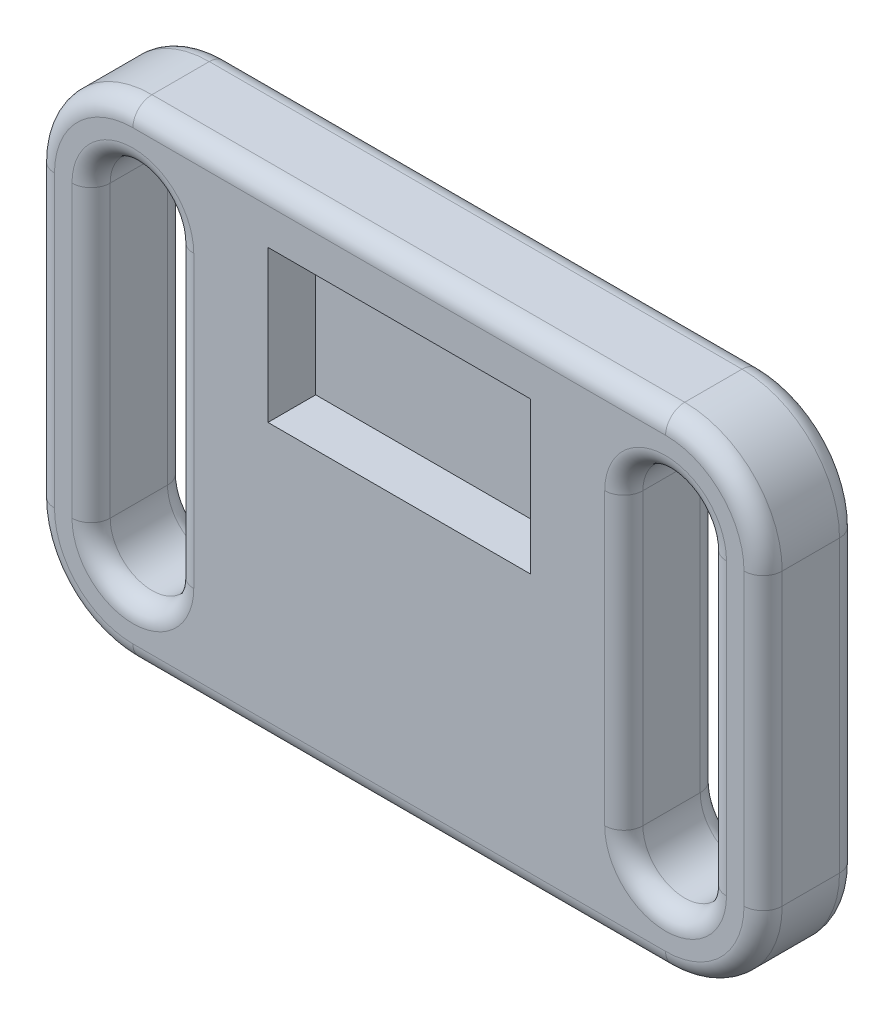
SolidWorks part; units mm, degrees
ref_plane "Front Plane" through (0, 0, 0) normal (0, 0, 1) x (1, 0, 0)
ref_plane "Top Plane" through (0, 0, 0) normal (0, 1, 0) x (1, 0, 0)
ref_plane "Right Plane" through (0, 0, 0) normal (1, 0, 0) x (0, 0, -1)
sketch "Sketch1" plane through (0, 0, 0) normal (0, 0, 1) x (1, 0, 0)
  line L0 (-152.4, -60.7667) -> (-152.4, 60.7667)
  line L1 (-152.4, -101.6) -> (152.4, -101.6) construction
  line L2 (-152.4, -101.6) -> (-152.4, 101.6) construction
  line L3 (-152.4, 101.6) -> (152.4, 101.6) construction
  line L4 (152.4, -101.6) -> (152.4, 101.6) construction
  line L5 (-152.4, -101.6) -> (152.4, 101.6) construction
  line L6 (-152.4, 101.6) -> (152.4, -101.6) construction
  line L7 (-111.5667, 101.6) -> (111.5667, 101.6)
  line L8 (0, 101.6) -> (0, -101.6) construction
  line L9 (152.4, 0) -> (-152.4, 0) construction
  line L10 (-152.4, -101.6) -> (152.4, 101.6) construction
  line L11 (-152.4, -101.6) -> (152.4, -101.6) construction
  line L12 (-111.5667, -101.6) -> (111.5667, -101.6)
  line L13 (152.4, -101.6) -> (-152.4, 101.6) construction
  line L14 (152.4, 101.6) -> (-152.4, -101.6) construction
  line L15 (152.4, -101.6) -> (-152.4, 101.6) construction
  line L16 (152.4, -101.6) -> (152.4, 101.6) construction
  line L17 (152.4, -60.7667) -> (152.4, 60.7667)
  line L18 (-129.0667, 60.7667) -> (-152.4, 60.7667) construction
  line L19 (-129.0667, 60.7667) -> (-94.0667, 60.7667) construction
  line L20 (-129.0667, 60.7667) -> (-129.0667, -60.7667)
  line L21 (-129.0667, -60.7667) -> (-94.0667, -60.7667) construction
  line L22 (-94.0667, 60.7667) -> (-94.0667, -60.7667)
  line L23 (129.0667, 60.7667) -> (129.0667, -60.7667)
  line L24 (94.0667, 60.7667) -> (94.0667, -60.7667)
  arc A0 (-152.4, 60.7667) -> (-111.5667, 101.6) centre (-111.5667, 60.7667) cw
  arc A1 (-152.4, -60.7667) -> (-111.5667, -101.6) centre (-111.5667, -60.7667) ccw
  arc A2 (152.4, -60.7667) -> (111.5667, -101.6) centre (111.5667, -60.7667) cw
  arc A3 (152.4, 60.7667) -> (111.5667, 101.6) centre (111.5667, 60.7667) ccw
  arc A4 (-129.0667, 60.7667) -> (-94.0667, 60.7667) centre (-111.5667, 60.7667) cw
  arc A5 (-129.0667, -60.7667) -> (-94.0667, -60.7667) centre (-111.5667, -60.7667) ccw
  arc A6 (129.0667, -60.7667) -> (94.0667, -60.7667) centre (111.5667, -60.7667) cw
  arc A7 (129.0667, 60.7667) -> (94.0667, 60.7667) centre (111.5667, 60.7667) ccw
  point P0 (0, 0)
  point P17 (0, 0)
  dimension "D1" = 203.2
  dimension "D2" = 304.8
  dimension "D3" = 35
  dimension "D4" = 23.3333
extrude "Steering Wheel Body" add sketch "Sketch1" along normal mid plane 40
fillet "Fillet1" radius 8 32 edges at (111.5667, 78.2667, -20) (129.0667, 0, -20) (111.5667, -78.2667, -20) (94.0667, 0, -20) (-111.5667, -78.2667, -20) (-129.0667, 0, -20) (-111.5667, 78.2667, -20) (-94.0667, 0, -20) (-152.4, 0, -20) (-140.4402, -89.6402, -20) (0, -101.6, -20) (140.4402, -89.6402, -20) (152.4, 0, -20) (140.4402, 89.6402, -20) (0, 101.6, -20) (-140.4402, 89.6402, -20) (129.0667, 0, 20) (111.5667, 78.2667, 20) (94.0667, 0, 20) (111.5667, -78.2667, 20) (0, 101.6, 20) (140.4402, 89.6402, 20) (152.4, 0, 20) (140.4402, -89.6402, 20) (0, -101.6, 20) (-140.4402, -89.6402, 20) (-152.4, 0, 20) (-140.4402, 89.6402, 20) (-129.0667, 0, 20) (-111.5667, -78.2667, 20) (-94.0667, 0, 20) (-111.5667, 78.2667, 20)
sketch "Sketch3" plane through (0, 0, 0) normal (0, 0, 1) x (1, 0, 0)
  line L0 (0, 0) -> (0, 101.6) construction
  line L1 (-54.9926, 15) -> (54.9926, 15)
  line L2 (-54.9926, 15) -> (-54.9926, 78.5)
  line L3 (-54.9926, 78.5) -> (54.9926, 78.5)
  line L4 (54.9926, 15) -> (54.9926, 78.5)
  line L5 (111.5667, 101.6) -> (-111.5667, 101.6) construction
  line L6 (0, 0) -> (152.4, 0) construction
  line L7 (152.4, -60.7667) -> (152.4, 60.7667) construction
  line L8 (-94.0667, -60.7667) -> (-94.0667, 60.7667) construction
  line L9 (-54.9926, 15) -> (54.9926, 78.5) construction
  point P9 (0, 15)
  dimension "D3" = 15
  dimension "D1" = 127
  dimension "D2" = 30
extrude "LCD Cutout" cut sketch "Sketch3" against normal blind 20 from surface starting at face at (111.5667, 0, 20)
sketch "Sketch5" plane through (0, 0, 0) normal (0, 0, 1) x (1, 0, 0)
  line L0 (0, 0) -> (0, 41.9601) construction
  circle A0 centre (0, 0) radius 41.9601 construction
  point P5 (0, 41.9601)
  dimension "D1" = 83.9201
hole_wizard "M5x0.8 Tapped Hole1" positions "Sketch6" profile "Sketch7" tap size "M5x0.8" standard "ANSI Metric"
sketch "Sketch6" plane through (0, 0, -20) normal (0, 0, -1) x (-1, 0, 0)
  point P0 (0, 41.9601)
sketch "Sketch7" plane through (0, 41.9601, -20) normal (1, 0, 0) x (0, 1, 0)
  line L0 (0, 0) -> (0, 9.6618)
  line L1 (0, 9.6618) -> (2.1, 8.4)
  line L2 (2.1, 8.4) -> (2.1, 0)
  line L5 (2.1, 0) -> (0, 0)
  line L10 (0, 9.6618) -> (-2.1, 8.4) construction
  line L11 (0, -6.35) -> (0, 107.95) construction
  dimension "Tap Drill Dia." = 4.2
  dimension "Tap Drill Depth" = 8.4
  dimension "Drill Angle" = 118
sketch "Sketch8" plane through (0, 0, 0) normal (0, 1, 0) x (1, 0, 0)
  line L0 (0, 52.4568) -> (0, -56.5569) construction
pattern_circular "CirPattern1" count 9 over 360 about axis through (0, 0, -52.4568) along (0, 0, 1) of "M5x0.8 Tapped Hole1"
equation "\"Steering Wheel Height\"= 8in"
equation "\"D1@Sketch1\"=\"Steering Wheel Height\""
equation "\"Steering Wheel Width\"= 12in"
equation "\"D2@Sketch1\"=\"Steering Wheel Width\""
equation "\"Steering Wheel Thickness\"= 35mm"
equation "\"Hand Cutout Width\"= 35mm"
equation "\"D3@Sketch1\"=\"Hand Cutout Width\""
equation "\"D4@Sketch1\"=\"Hand Cutout Width\"*(2/3)"
equation "\"LCD Width\"= \"LCD Size\" * cos ( 30deg )"
equation "\"LCD Height\"= \"LCD Size\" * sin ( 30deg )"
equation "\"LCD Thickness\"= 2cm'Exact thickness is unknown at this time for the LCD specced out"
equation "\"D1@LCD Cutout\" = \"LCD Thickness\""
equation "\"LCD Size\"= 5in"
equation "\"D1@Sketch3\"=\"LCD Size\""
equation "\"Quick Release Diameter\"=83.9201"
equation "\"D1@Sketch5\"=\"Quick Release Diameter\""
equation "\"Number of Holes on Quick Release\"=9"
